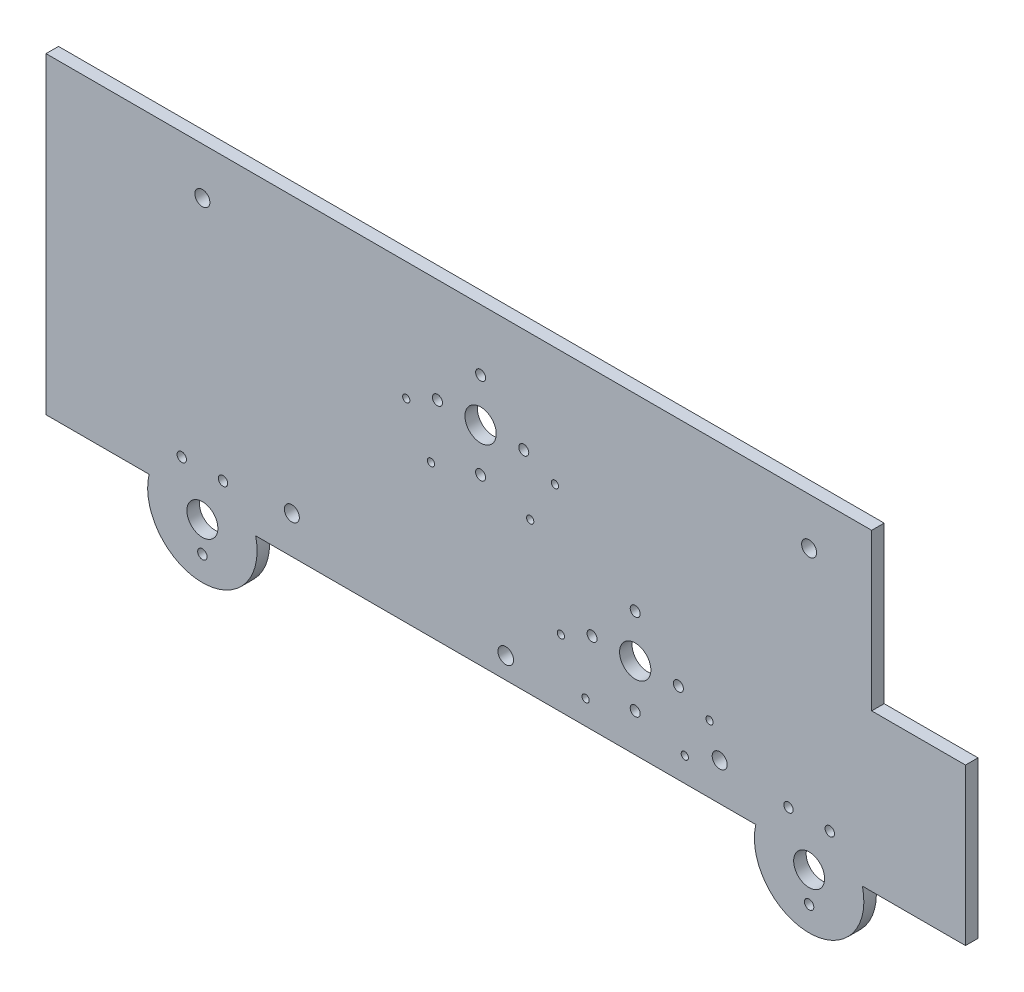
SolidWorks part; units mm, degrees
ref_plane "Front Plane" through (0, 0, 0) normal (0, 0, 1) x (1, 0, 0)
ref_plane "Top Plane" through (0, 0, 0) normal (0, 1, 0) x (1, 0, 0)
ref_plane "Right Plane" through (0, 0, 0) normal (1, 0, 0) x (0, 0, -1)
sketch "Sketch2" plane through (0, 0, 0) normal (0, 0, 1) x (1, 0, 0)
  line L0 (-123.19, -36.83) -> (-123.19, -31.75) construction
  line L1 (-186.69, -31.75) -> (186.69, -31.75)
  line L2 (-186.69, -31.75) -> (-186.69, 31.75)
  line L3 (-186.69, 31.75) -> (186.69, 31.75)
  line L4 (186.69, -31.75) -> (186.69, 31.75)
  line L5 (-186.69, -31.75) -> (186.69, 31.75) construction
  line L6 (-186.69, 31.75) -> (186.69, -31.75) construction
  line L7 (0, 0) -> (0, -31.75) construction
  line L8 (123.19, -36.83) -> (123.19, -31.75) construction
  line L16 (-186.69, 31.75) -> (186.69, 31.75)
  line L17 (-186.69, 31.75) -> (-186.69, 95.25)
  line L18 (-186.69, 95.25) -> (186.69, 95.25)
  line L19 (186.69, 31.75) -> (186.69, 95.25)
  circle A0 centre (-123.19, -36.83) radius 6.2865
  circle A1 centre (123.19, -36.83) radius 6.2865
  circle A2 centre (-123.19, -36.83) radius 22.225
  circle A3 centre (123.19, -36.83) radius 22.225
  circle A4 centre (-123.19, 76.2) radius 3.048
  circle A5 centre (123.19, 76.2) radius 3.048
  circle A7 centre (86.868, -16.51) radius 3.048
  circle A8 centre (-86.868, -16.51) radius 3.048
  point P0 (0, 0)
  point P27 (-86.868, -16.51)
  dimension "D3" = 123.19
  dimension "D5" = 5.08
  dimension "D7" = 63.5
  dimension "D8" = 44.45
  dimension "D4" = 12.573
  dimension "D9" = 12.573
  dimension "D10" = 44.45
  dimension "D13" = 6.096
  dimension "D14" = 6.096
  dimension "D19" = 6.096
  dimension "D20" = 6.096
  dimension "D1" = 63.5
  dimension "D2" = 373.38
  dimension "D6" = 123.19
  dimension "D11" = 107.95
  dimension "D12" = 107.95
  dimension "D15" = 86.868
  dimension "D16" = 15.24
  dimension "D17" = 15.24
  dimension "D18" = 86.868
extrude "Boss-Extrude1" add sketch "Sketch2" against normal blind 5.0749 contours A1 L1 L4 L3 L2 A0 | L3 L19 L18 L17 | A2 | A3 region at (0, 1.2473, 0) region at (0, 63.4687, 0)
extrude "Cut-Extrude11" cut sketch "Sketch2<4>" against normal through all contours L1 A0 | L1 A1 | A0 | A1 region at (-123.19, -37.1167, 0) region at (123.19, -37.1167, 0)
sketch "Sketch2<4>" plane through (0, 0, 0) normal (0, 0, 1) x (1, 0, 0) same geometry as "Sketch2"
ref_plane "Plane1" through (-186.69, 95.25, 0) normal (0, 1, 0) x (1, 0, 0)
ref_plane "Plane2" through (0, 0, -5.0749) normal (0, 0, -1) x (-1, 0, 0)
sketch "Sketch3" plane through (0, 0, 0) normal (0, 0, 1) x (1, 0, 0)
  line L0 (-101.5534, -31.75) -> (101.5534, -31.75) construction
  circle A0 centre (-10.2093, 52.8905) radius 22.86
  circle A1 centre (52.5741, 1.27) radius 22.86
  circle A2 centre (-10.2093, 52.8905) radius 6.35
  circle A3 centre (52.5741, 1.27) radius 6.35
  circle A4 centre (-27.7353, 52.8905) radius 2.032
  circle A5 centre (-10.2093, 70.4165) radius 2.032
  circle A6 centre (-10.2093, 35.3645) radius 2.032
  circle A7 centre (7.3167, 52.8905) radius 2.032
  circle A8 centre (35.0481, 1.27) radius 2.032
  circle A9 centre (70.1001, 1.27) radius 2.032
  circle A10 centre (52.5741, 18.796) radius 2.032
  circle A11 centre (52.5741, -16.256) radius 2.032
  point P0 (-10.2093, 52.8905)
  point P1 (52.5741, 1.27)
  dimension "D5" = 45.72
  dimension "D6" = 12.7
  dimension "D7" = 12.7
  dimension "D12" = 4.064
  dimension "D15" = 4.064
  dimension "D18" = 33.02
  dimension "D2" = 144.272
  dimension "D3" = 80.2385
  dimension "D4" = 81.28
  dimension "D8" = 17.526
  dimension "D9" = 17.526
  dimension "D10" = 17.526
  dimension "D11" = 17.526
  dimension "D13" = 17.526
  dimension "D14" = 17.526
  dimension "D16" = 17.526
  dimension "D17" = 17.526
extrude "Cut-Extrude12" cut sketch "Sketch3" against normal through all contours A2 | A7 | A3 | A9 | A10 | A8 | A5 | A4 | A6 | A11 region at (-10.2093, 52.8905, 0) region at (52.5741, 1.27, 0) region at (7.3167, 52.8905, 0) region at (35.0481, 1.27, 0) region at (70.1001, 1.27, 0) region at (52.5741, 18.796, 0)
sketch "Sketch5" plane through (0, 0, 0) normal (0, 0, 1) x (1, 0, 0)
  line L0 (-10.2093, 52.8905) -> (-10.2093, 22.1565) construction
  line L1 (52.5741, 1.27) -> (52.5741, -29.464) construction
  line L2 (-40.3931, 47.101) -> (19.9745, 47.101) construction
  line L3 (-30.3465, 29.6726) -> (9.9278, 29.6726) construction
  line L4 (32.437, -21.948) -> (72.7113, -21.948) construction
  line L5 (22.3904, -4.5195) -> (82.7579, -4.5195) construction
  circle A0 centre (-10.2093, 52.8905) radius 30.734
  circle A1 centre (52.5741, 1.27) radius 30.734
  circle A2 centre (-30.3465, 29.6726) radius 1.4732
  circle A3 centre (9.9278, 29.6726) radius 1.4732
  circle A4 centre (-40.3931, 47.101) radius 1.4732
  circle A5 centre (19.9745, 47.101) radius 1.4732
  circle A6 centre (32.437, -21.948) radius 1.4732
  circle A7 centre (72.7113, -21.948) radius 1.4732
  circle A8 centre (22.3904, -4.5195) radius 1.4732
  circle A9 centre (82.7579, -4.5195) radius 1.4732
  circle A10 centre (-10.2093, 22.1565) radius 1.4732
  circle A11 centre (52.5741, -29.464) radius 1.4732
  dimension "D1" = 61.468
  dimension "D2" = 61.468
  dimension "D5" = 2.9464
  dimension "D8" = 2.9464
  dimension "D3" = 20.1168
  dimension "D4" = 20.1168
  dimension "D6" = 21.4941
  dimension "D7" = 21.4941
extrude "Cut-Extrude13" cut sketch "Sketch5" against normal through all contours A1 A8 | A1 A8 | A1 A9 | A1 A9 | A1 A7 | A4 | A2 | A3 | A5 | A6 | A7 region at (23.0106, -4.4005, 0) region at (21.7826, -4.6361, 0) region at (83.3657, -4.6361, 0) region at (82.1377, -4.4005, 0) region at (72.2975, -21.4709, 0)
sketch "Sketch7" plane through (0, 0, 0) normal (0, 0, 1) x (1, 0, 0)
  line L0 (-123.19, -36.83) -> (-123.19, -59.055) construction
  line L1 (-131.572, -19.05) -> (-114.808, -19.05) construction
  line L2 (123.19, -36.83) -> (123.19, -59.055) construction
  line L3 (114.808, -19.05) -> (131.572, -19.05)
  circle A0 centre (-123.19, -36.83) radius 22.225 construction
  circle A1 centre (-123.19, -49.022) radius 1.905
  circle A2 centre (-131.572, -19.05) radius 1.905
  circle A3 centre (-114.808, -19.05) radius 1.905
  circle A4 centre (123.19, -36.83) radius 22.225 construction
  circle A5 centre (123.19, -49.022) radius 1.905
  circle A6 centre (114.808, -19.05) radius 1.905
  circle A7 centre (131.572, -19.05) radius 1.905
  point P15 (-123.19, -19.05)
  point P23 (123.19, -19.05)
  dimension "D4" = 3.81
  dimension "D6" = 3.81
  dimension "D1" = 12.192
  dimension "D2" = 17.78
  dimension "D3" = 16.764
  dimension "D5" = 12.192
  dimension "D7" = 17.78
  dimension "D8" = 16.764
extrude "Cut-Extrude14" cut sketch "Sketch7" against normal through all contours A2 | A1 | A6 | A7 | A5 | A3 region at (131.572, -17.1989, 0) region at (112.9569, -19.05, 0) region at (-123.19, -49.022, 0) region at (-131.572, -19.05, 0) region at (123.19, -49.022, 0)
sketch "Sketch8" plane through (0, 0, 0) normal (0, 0, 1) x (1, 0, 0)
  line L0 (0, 0) -> (0, -31.75) construction
  circle A0 centre (0, -23.114) radius 3.175
  dimension "D2" = 6.35
  dimension "D1" = 8.636
extrude "Cut-Extrude15" cut sketch "Sketch8" against normal through all contours A0
sketch "Sketch9" plane through (0, 0, 0) normal (0, 0, 1) x (1, 0, 0)
  line L6 (186.69, 95.25) -> (148.59, 95.25)
  line L7 (186.69, 95.25) -> (186.69, 31.75)
  line L8 (186.69, 31.75) -> (148.59, 31.75)
  line L9 (148.59, 95.25) -> (148.59, 31.75)
  dimension "D2" = 38.1
  dimension "D3" = 63.5
extrude "Cut-Extrude16" cut sketch "Sketch9" against normal blind 5.08
